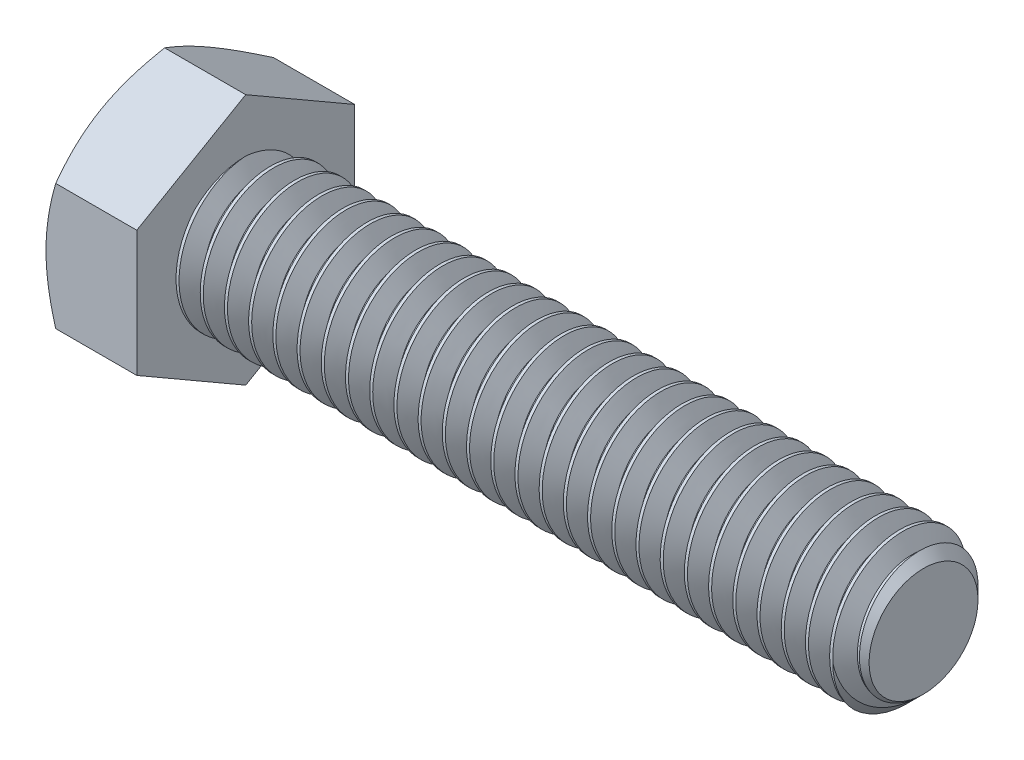
SolidWorks part; units mm, degrees
material "AISI 304"
ref_plane "Front Plane" through (0, 0, 0) normal (0, 0, 1) x (1, 0, 0)
ref_plane "Top Plane" through (0, 0, 0) normal (0, 1, 0) x (1, 0, 0)
ref_plane "Right Plane" through (0, 0, 0) normal (1, 0, 0) x (0, 0, -1)
sketch "Sketch1" plane through (0, 0, 0) normal (0, 0, 1) x (1, 0, 0)
  line L0 (-25.2016, 0) -> (25.2016, 0) construction
  line L1 (25.2016, 4.7625) -> (25.2016, -4.7625) construction
  line L2 (-19.2484, 7.1437) -> (-19.2484, -7.1437) construction
  line L3 (-25.2016, 7.1437) -> (-25.2016, -7.1437) construction
  point P9 (-19.2484, 0)
  point P10 (19.6453, -4.7625)
  dimension "D1" = 5.5562
  dimension "Screw Dia" = 9.525
  dimension "Hex" = 14.2875
  dimension "Head Ht" = 5.9531
  dimension "Screw Lenght" = 44.45
ref_plane "Plane2" through (25.2016, 0, 0) normal (1, 0, 0) x (0, 0, -1)
sketch "Sketch5" plane through (25.2016, 0, 0) normal (1, 0, 0) x (0, 0, -1)
  circle A0 centre (0, 0) radius 4.7625
extrude "Boss-Extrude3" add sketch "Sketch5" against normal up to vertex (44.45 mm away) up to point (-19.2484, 0, 0)
sketch "Sketch9" plane through (25.2016, 0, 0) normal (1, 0, 0) x (0, 0, -1)
  circle A1 centre (0, 0) radius 4.7625
  circle A2 centre (0, 0) radius 4.7625
  dimension "D1" = 0
curve "Helix/Spiral1" pitch 1.5875 height 46.0375 turns 29 parameters "Pitch"=1.5875
chamfer "Chamfer1" distance 1.1906 angle 45 1 edges at (25.2016, 0, -4.7625)
sketch "Sketch10" plane through (0, 0, 0) normal (0, 0, 1) x (1, 0, 0)
  line L0 (25.2016, 4.7625) -> (25.7969, 3.7314)
  line L1 (25.7969, 3.7314) -> (25.9953, 3.7314)
  line L2 (25.9953, 3.7314) -> (26.5906, 4.7625)
  line L3 (25.2016, 4.7625) -> (26.5906, 4.7625)
  line L4 (25.8961, 4.7625) -> (25.8961, 3.7314) construction
  line L5 (25.4992, 4.2469) -> (26.293, 4.2469) construction
  dimension "D1" = 60
  dimension "D2" = 0.1984
  dimension "D3" = 0.7937
sweep "Cut-Sweep1" cut profiles "Sketch10" path "Helix/Spiral1"
sketch "Sketch6" plane through (-19.2484, 0, 0) normal (-1, 0, 0) x (0, 0, 1)
  line L0 (0, 7.1437) -> (0, -7.1437) construction
  line L1 (7.1437, 4.1244) -> (0, 8.2489)
  line L2 (0, 8.2489) -> (-7.1437, 4.1244)
  line L3 (-7.1437, 4.1244) -> (-7.1437, -4.1244)
  line L4 (-7.1437, -4.1244) -> (0, -8.2489)
  line L5 (0, -8.2489) -> (7.1438, -4.1244)
  line L6 (7.1438, -4.1244) -> (7.1437, 4.1244)
  circle A0 centre (0, 0) radius 7.1438 construction
extrude "Boss-Extrude4" add sketch "Sketch6" along normal up to vertex (5.9531 mm away) up to point (-25.2016, -7.1437, 0)
sketch "Sketch7" plane through (-25.2016, 0, 0) normal (-1, 0, 0) x (0, 0, 1)
  circle A0 centre (0, 0) radius 7.1438 construction
  circle A1 centre (0, 0) radius 7.1438
sketch "Sketch8" plane through (-25.2016, 0, 0) normal (-1, 0, 0) x (0, 0, 1)
  circle A0 centre (0, 0) radius 7.1438 construction
  circle A1 centre (0, 0) radius 7.1438
extrude "Cut-Extrude3" cut sketch "Sketch8" against normal through all draft 60 flip side to cut
equation "\"D2@Sketch10\" = \"Pitch@Helix/Spiral1\"*.125"
equation "\"D3@Sketch10\" = \"Pitch@Helix/Spiral1\"*.5"
equation "\"D3@Helix/Spiral1\" = \"Screw Lenght@Sketch1\"+\"Pitch@Helix/Spiral1\""
equation "\"D1@Chamfer1\" = \"Pitch@Helix/Spiral1\"*.75"
equation "\"D1@Sketch1\" = \"Pitch@Helix/Spiral1\"*3.5"
